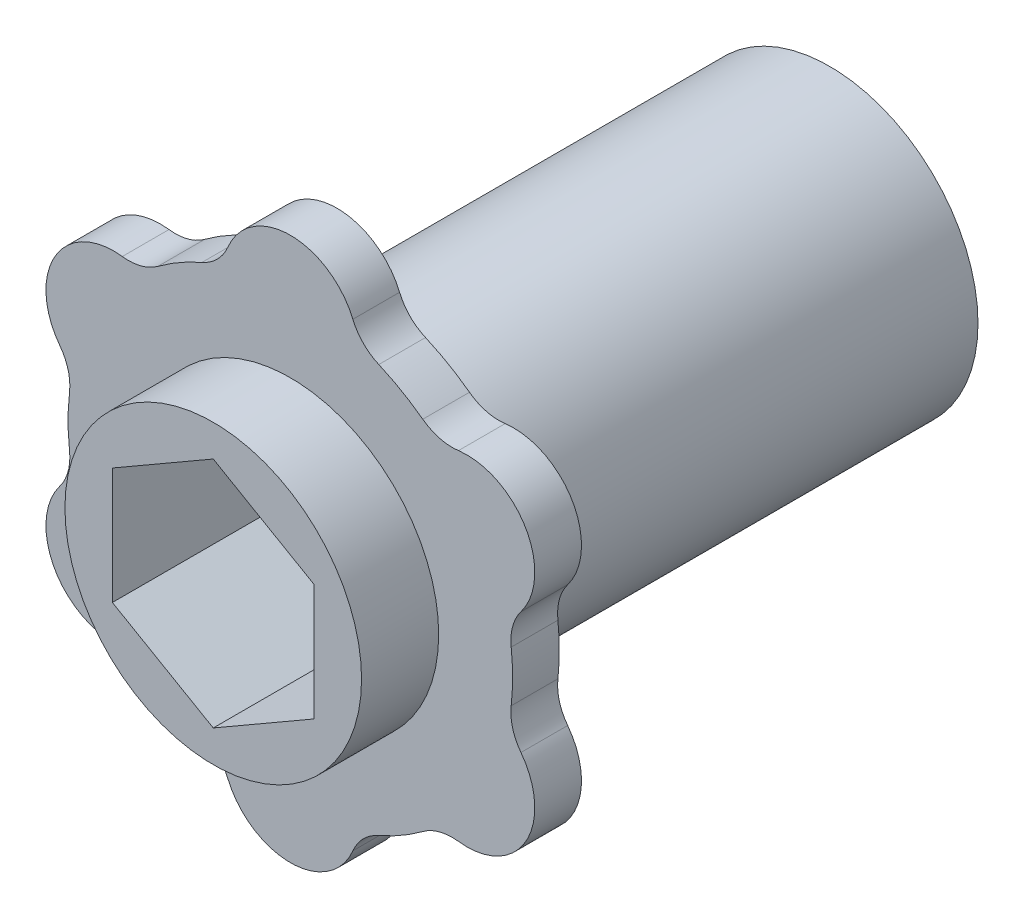
SolidWorks part; units mm, degrees
material "PET"
ref_plane "Front Plane" through (0, 0, 0) normal (0, 0, 1) x (1, 0, 0)
ref_plane "Top Plane" through (0, 0, 0) normal (0, 1, 0) x (1, 0, 0)
ref_plane "Right Plane" through (0, 0, 0) normal (1, 0, 0) x (0, 0, -1)
sketch "Sketch1" plane through (0, 0, 0) normal (0, 0, 1) x (1, 0, 0)
  line L0 (0, -13.0969) -> (0, 13.0969) construction
  line L1 (0, 7.479) -> (-6.477, 3.7395)
  line L2 (-6.477, 3.7395) -> (-6.477, -3.7395)
  line L3 (-6.477, -3.7395) -> (0, -7.479)
  line L4 (0, -7.479) -> (6.477, -3.7395)
  line L5 (6.477, -3.7395) -> (6.477, 3.7395)
  line L6 (6.477, 3.7395) -> (0, 7.479)
  arc A0 (-13.9434, 3.0582) -> (-13.9434, -3.0582) centre (0, 0) ccw
  circle A1 centre (0, 0) radius 6.477 construction
  arc A2 (4.3232, 13.6044) -> (-4.3232, 13.6044) centre (0, 13.0969) ccw
  arc A3 (13.9434, 3.0582) -> (9.6201, 10.5462) centre (11.3422, 6.5484) ccw
  arc A4 (9.6201, -10.5462) -> (13.9434, -3.0582) centre (11.3422, -6.5484) ccw
  arc A5 (-4.3232, -13.6044) -> (4.3232, -13.6044) centre (0, -13.0969) ccw
  arc A6 (-13.9434, -3.0582) -> (-9.6201, -10.5462) centre (-11.3422, -6.5484) ccw
  arc A7 (-9.6201, 10.5462) -> (-13.9434, 3.0582) centre (-11.3422, 6.5484) ccw
  arc A8 (-4.3232, 13.6044) -> (-9.6201, 10.5462) centre (0, 0) ccw
  arc A9 (9.6201, 10.5462) -> (4.3232, 13.6044) centre (0, 0) ccw
  arc A10 (13.9434, -3.0582) -> (13.9434, 3.0582) centre (0, 0) ccw
  arc A11 (4.3232, -13.6044) -> (9.6201, -10.5462) centre (0, 0) ccw
  arc A12 (-9.6201, -10.5462) -> (-4.3232, -13.6044) centre (0, 0) ccw
  point P24 (0, 0)
  dimension "D1" = 28.5496
  dimension "D2" = 12.954
  dimension "D3" = 8.7058
  dimension "D4" = 13.0969
  dimension "D6" = 26.1937
  dimension "D5" = 6
extrude "Boss-Extrude1" add sketch "Sketch1" along normal mid plane 2.9997
sketch "Sketch2" plane through (0, 0, 1.4999) normal (0, 0, 1) x (1, 0, 0)
  line L1 (0, 7.479) -> (-6.477, 3.7395)
  line L2 (-6.477, 3.7395) -> (-6.477, -3.7395)
  line L3 (-6.477, -3.7395) -> (0, -7.479)
  line L4 (0, -7.479) -> (6.477, -3.7395)
  line L5 (6.477, -3.7395) -> (6.477, 3.7395)
  line L6 (6.477, 3.7395) -> (0, 7.479)
  circle A0 centre (0, 0) radius 6.477 construction
  circle A1 centre (0, 0) radius 9.525
  dimension "D1" = 19.05
extrude "Boss-Extrude2" add sketch "Sketch2" along normal blind 4.953
sketch "Sketch3" plane through (0, 0, -1.4999) normal (0, 0, -1) x (-1, 0, 0)
  line L1 (0, 7.479) -> (-6.477, 3.7395)
  line L2 (-6.477, 3.7395) -> (-6.477, -3.7395)
  line L3 (-6.477, -3.7395) -> (0, -7.479)
  line L4 (0, -7.479) -> (6.477, -3.7395)
  line L5 (6.477, -3.7395) -> (6.477, 3.7395)
  line L6 (6.477, 3.7395) -> (0, 7.479)
  circle A0 centre (0, 0) radius 6.477 construction
  circle A1 centre (0, 0) radius 9.525
  dimension "D1" = 19.05
extrude "Boss-Extrude3" add sketch "Sketch3" along normal blind 31.6332
fillet "Fillet1" radius 3.175 12 edges at (9.6201, 10.5462, 0) (13.9434, 3.0582, 0) (13.9434, -3.0582, 0) (9.6201, -10.5462, 0) (4.3232, -13.6044, 0) (-4.3232, -13.6044, 0) (-9.6201, -10.5462, 0) (-13.9434, -3.0582, 0) (-13.9434, 3.0582, 0) (-9.6201, 10.5462, 0) (-4.3232, 13.6044, 0) (4.3232, 13.6044, 0)
